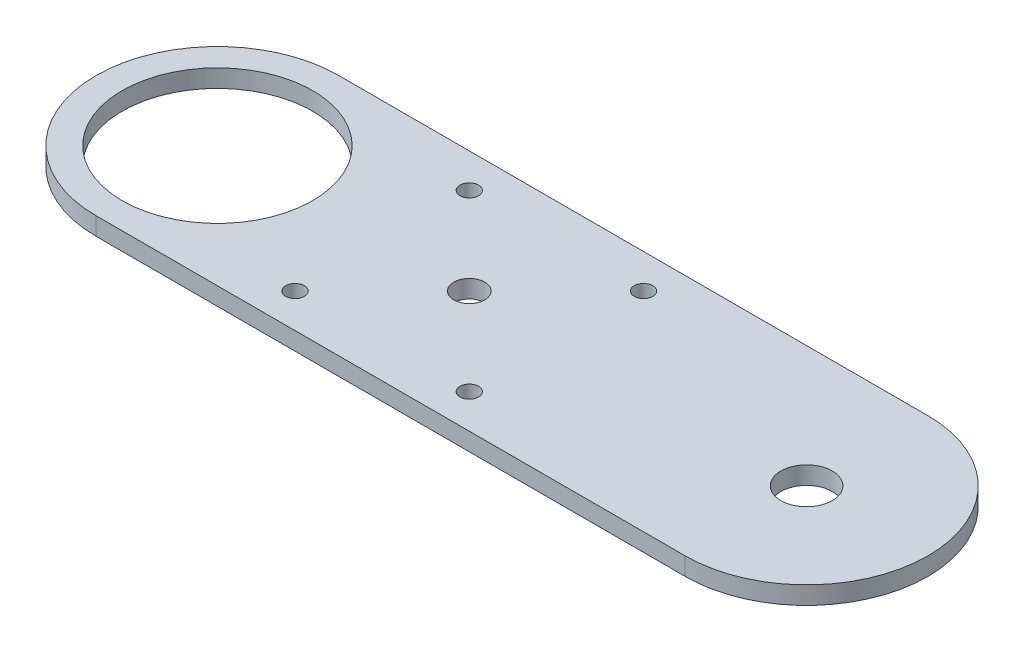
SolidWorks part; units mm, degrees
ref_plane "Front Plane" through (0, 0, 0) normal (0, 0, 1) x (1, 0, 0)
ref_plane "Top Plane" through (0, 0, 0) normal (0, 1, 0) x (1, 0, 0)
ref_plane "Right Plane" through (0, 0, 0) normal (1, 0, 0) x (0, 0, -1)
sketch "Sketch1" plane through (0, 0, 0) normal (0, 1, 0) x (1, 0, 0)
  line L0 (0, 0) -> (104.8004, 0) construction
  line L1 (0, 21.59) -> (104.8004, 21.59)
  line L2 (0, -21.59) -> (104.8004, -21.59)
  line L3 (52.4002, 21.59) -> (52.4002, -21.59) construction
  line L4 (0, 0) -> (104.8004, 0) construction
  line L5 (29.3004, -15.5) -> (60.3004, -15.5) construction
  line L6 (29.3004, -15.5) -> (29.3004, 15.5) construction
  line L7 (29.3004, 15.5) -> (60.3004, 15.5) construction
  line L8 (60.3004, -15.5) -> (60.3004, 15.5) construction
  line L9 (29.3004, -15.5) -> (60.3004, 15.5) construction
  line L10 (29.3004, 15.5) -> (60.3004, -15.5) construction
  line L11 (29.3004, 0) -> (60.3004, 0) construction
  line L12 (44.8004, -15.5) -> (44.8004, 15.5) construction
  arc A0 (0, 21.59) -> (0, -21.59) centre (0, 0) ccw
  arc A1 (104.8004, -21.59) -> (104.8004, 21.59) centre (104.8004, 0) ccw
  circle A2 centre (0, 0) radius 16.9545
  circle A3 centre (104.8004, 0) radius 4.572
  circle A4 centre (44.8004, 0) radius 2.75
  circle A5 centre (29.3004, -15.5) radius 1.651
  circle A6 centre (29.3004, 15.5) radius 1.651
  circle A7 centre (60.3004, 15.5) radius 1.651
  circle A8 centre (60.3004, -15.5) radius 1.651
  point P3 (52.4002, 0)
  dimension "D2" = 21.59
  dimension "D3" = 33.909
  dimension "D4" = 9.144
  dimension "D5" = 5.5
  dimension "D7" = 3.302
  dimension "D10" = 3.302
  dimension "D1" = 104.8004
  dimension "D6" = 60
  dimension "D8" = 31
  dimension "D9" = 31
extrude "Boss-Extrude1" add sketch "Sketch1" along normal blind 3.175
